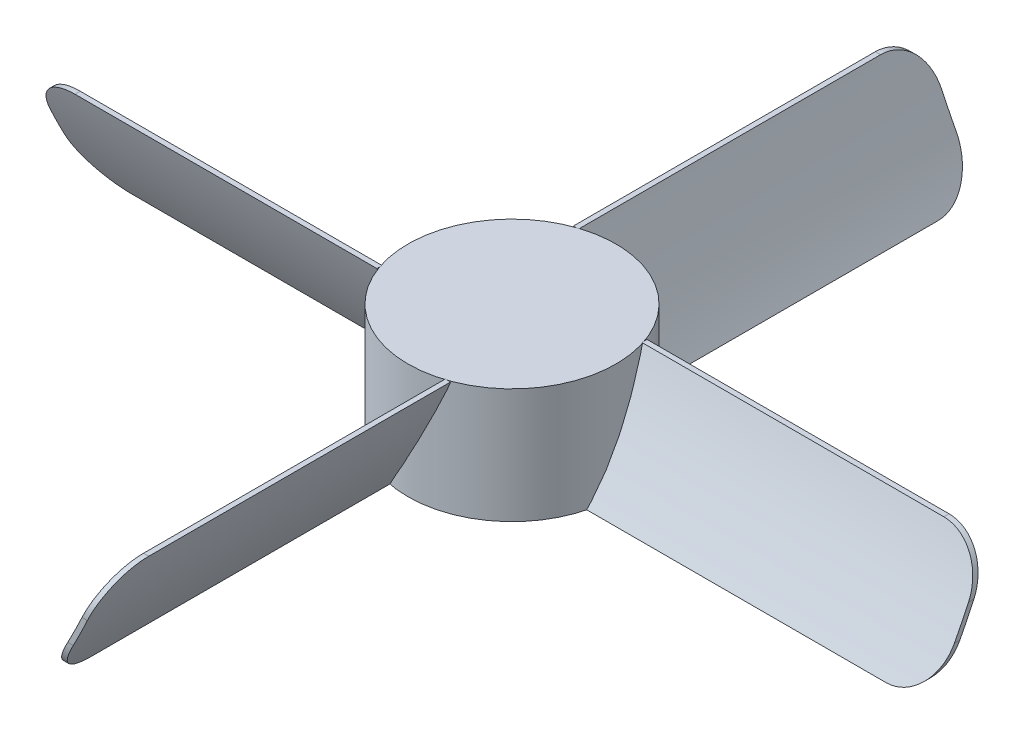
SolidWorks part; units mm, degrees
ref_plane "Front Plane" through (0, 0, 0) normal (0, 0, 1) x (1, 0, 0)
ref_plane "Top Plane" through (0, 0, 0) normal (0, 1, 0) x (1, 0, 0)
ref_plane "Right Plane" through (0, 0, 0) normal (1, 0, 0) x (0, 0, -1)
sketch "Sketch7" plane through (0, 0, 0) normal (0, 0, 1) x (1, 0, 0)
  line L0 (5.9992, 0) -> (-5.9992, 0) construction
  line L1 (10.9077, 20) -> (10, 20)
  line L2 (0, 0) -> (1, 0)
  arc A0 (0, 0) -> (10, 20) centre (-97.3948, 61.1974) ccw
  arc A1 (10.9077, 20) -> (1, 0) centre (-97.3948, 61.1974) cw
  point P2 (0, 0)
  point P7 (44.319, 50.6244)
  point P11 (0, 0)
  point P12 (0, 0)
  point P13 (0, 0)
  point P14 (10.9077, 20)
  point P15 (0, 0)
  point P16 (0, 0)
  point P17 (0, 0)
  point P18 (0, 0)
  dimension "D3" = 10
extrude "Boss-Extrude2" add sketch "Sketch7" along normal blind 60 contours A0 L1 A1 L2
fillet "Fillet1" radius 7.5 2 edges at (0.5, 0, 60) (10.4539, 20, 60)
sketch "Sketch10" plane through (0, 0, 0) normal (0, 1, 0) x (1, 0, 0)
  line L0 (0, 0) -> (9.0039, 0)
  line L2 (10.9077, 0) -> (10, 0) construction
  line L3 (1, 0) -> (10.9077, 0) construction
  line L4 (4.5019, 0) -> (4.5019, 17.0863)
  circle A0 centre (4.5019, 17.0863) radius 18.0863
  point P10 (0, 0)
  point P12 (5.3118, 0)
  point P13 (4.5019, 0)
extrude "Boss-Extrude3" add sketch "Sketch10" along normal blind 20 separate body contours A0
pattern_circular "CirPattern1" count 4 over 360 about axis through (4.5019, 20, -17.0863) along (0, -1, 0) of bodies 102
equation "\"insidebladediameter\"=0.0361727"
equation "\"height\"=0.02"
equation "\"bladewidth\" = 0.001"
equation "\"insidebladeradius\" = \"insidebladediameter\" / 2"
equation "\"xtranslationblade\"=0.05"
equation "\"D1@Sketch7\"=\"bladewidth\""
equation "\"D2@Sketch7\"=\"height\""
equation "\"bladesize\"= 0.01"
equation "\"bladelength\"=0.06"
equation "\"D1@Boss-Extrude2\"=\"bladelength\""
equation "\"bladetipradius\"=0.0075"
equation "\"D1@Fillet1\"=\"bladetipradius\""
equation "\"D1@Sketch10\"=\"insidebladediameter\""
equation "\"fusedistance\"= \"insidebladeradius\" - 0.001"
equation "\"D2@Sketch10\"=\"fusedistance\""
equation "\"D1@Boss-Extrude3\"=\"height\""
equation "\"numberofblades\"=4"
equation "\"D1@CirPattern1\"=\"numberofblades\""
